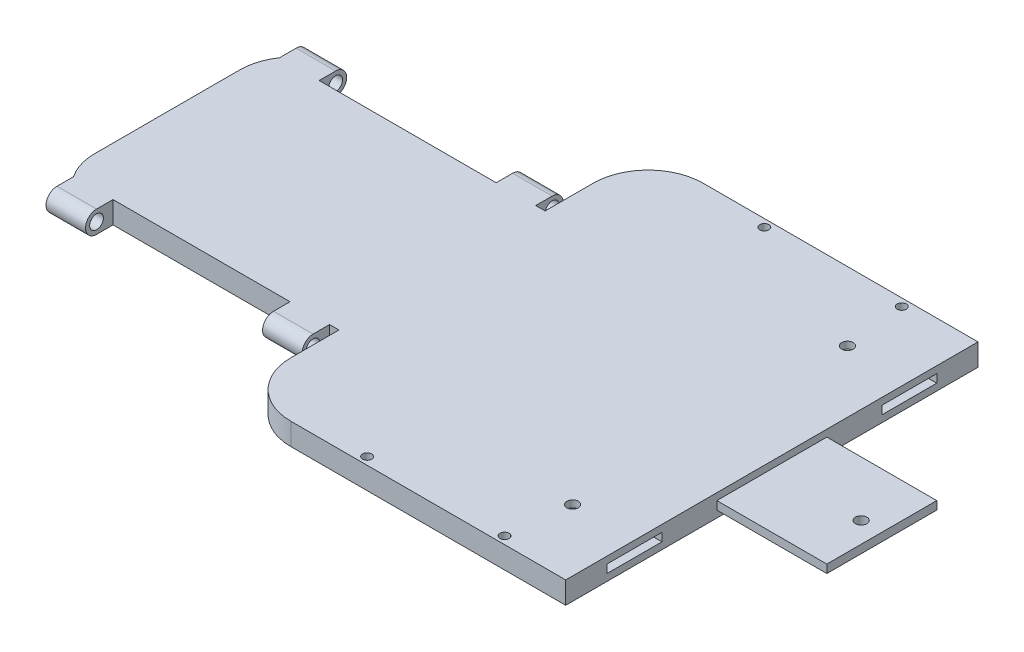
SolidWorks part; units mm, degrees
ref_plane "Front Plane" through (0, 0, 0) normal (0, 0, 1) x (1, 0, 0)
ref_plane "Top Plane" through (0, 0, 0) normal (0, 1, 0) x (1, 0, 0)
ref_plane "Right Plane" through (0, 0, 0) normal (1, 0, 0) x (0, 0, -1)
sketch "Sketch1" plane through (0, 0, 0) normal (0, 1, 0) x (1, 0, 0)
  line L0 (-120, -37.5) -> (-120, -75)
  line L1 (-120, 75) -> (0, 75)
  line L2 (-120, 75) -> (-120, 37.5)
  line L3 (-120, -75) -> (0, -75)
  line L5 (-120, 75) -> (0, 0) construction
  line L6 (0, 75) -> (0, -75)
  line L7 (-220, 37.5) -> (-120, 37.5)
  line L8 (-220, 37.5) -> (-220, -37.5)
  line L9 (-220, -37.5) -> (-120, -37.5)
  line L11 (-220, 37.5) -> (-120, -37.5) construction
  line L12 (-220, -37.5) -> (-120, 37.5) construction
  line L13 (-237.7651, 0) -> (0, 0) construction
  line L14 (0, 88.8927) -> (0, -90.7354) construction
  point P0 (0, 0)
  point P6 (-170, 0)
  dimension "D1" = 100
  dimension "D2" = 75
  dimension "D3" = 120
  dimension "D4" = 150
extrude "Boss-Extrude1" add sketch "Sketch1" along normal blind 8
ref_plane "Plane1" through (-170, 0, 0) normal (-1, 0, 0) x (0, 0, 1)
sketch "Sketch4" plane through (-170, 0, 0) normal (-1, 0, 0) x (0, 0, 1)
  line L0 (37.5, 8) -> (43.5, 8)
  line L1 (37.5, 0) -> (43.5, 0)
  line L2 (37.5, 8) -> (37.5, 0)
  line L3 (0, 17.6181) -> (0, -10.735) construction
  line L4 (-37.5, 0) -> (-43.5, 0)
  line L5 (-37.5, 8) -> (-37.5, 0)
  line L6 (-37.5, 8) -> (-43.5, 8)
  arc A0 (43.5, 0) -> (43.5, 8) centre (43.5, 4) ccw
  circle A1 centre (43.5, 4) radius 3.3
  circle A2 centre (-43.5, 4) radius 3.3
  arc A3 (-43.5, 0) -> (-43.5, 8) centre (-43.5, 4) cw
  dimension "D1" = 6
extrude "Boss-Extrude2" add sketch "Sketch4" along normal blind 46.584 and the other way blind 46.584
sketch "Sketch5" plane through (-170, 0, 0) normal (-1, 0, 0) x (0, 0, 1)
  line L9 (-43.5, 8) -> (-37.5, 8)
  line L10 (-37.5, 8) -> (-37.5, 0)
  line L11 (-37.5, 0) -> (-43.5, 0)
  line L12 (0, -5.7713) -> (0, 22.701) construction
  line L13 (37.5, 0) -> (43.5, 0)
  line L14 (37.5, 8) -> (37.5, 0)
  line L15 (43.5, 8) -> (37.5, 8)
  circle A20 centre (-43.5, 4) radius 3.3
  circle A21 centre (-43.5, 4) radius 3.3
  arc A22 (43.5, 8) -> (43.5, 0) centre (43.5, 4) cw
  arc A23 (-43.5, 8) -> (-43.5, 0) centre (-43.5, 4) ccw
  arc A24 (-43.5, 8) -> (-43.5, 0) centre (-43.5, 4) ccw
  circle A25 centre (43.5, 4) radius 3.3
  dimension "D1" = 0
  dimension "D2" = 0
extrude "Cut-Extrude1" cut sketch "Sketch5" against normal blind 32.2 and the other way blind 32.2
sketch "Sketch6" plane through (0, 0, 0) normal (1, 0, 0) x (0, 0, -1)
  line L0 (0, 8) -> (0, 0) construction
  line L1 (-75, 8) -> (75, 8) construction
  line L3 (-20, 5.5) -> (20, 5.5)
  line L4 (-20, 5.5) -> (-20, 2.5)
  line L5 (-20, 2.5) -> (20, 2.5)
  line L6 (20, 5.5) -> (20, 2.5)
  line L7 (-20, 5.5) -> (20, 2.5) construction
  line L8 (-20, 2.5) -> (20, 5.5) construction
  point P5 (0, 4)
  dimension "D1" = 40
  dimension "D2" = 2.5
  dimension "D3" = 3
extrude "Boss-Extrude3" add sketch "Sketch6" along normal blind 40
sketch "Sketch7" plane through (0, 5.5, 0) normal (0, 1, 0) x (1, 0, 0)
  line L0 (40, 20) -> (40, -20) construction
  circle A0 centre (32.75, 0) radius 2
  dimension "D1" = 4
  dimension "D2" = 7.25
extrude "Cut-Extrude2" cut sketch "Sketch7" against normal through all
sketch "Sketch8" plane through (0, 0, 0) normal (1, 0, 0) x (0, 0, -1)
  line L0 (0, 13.5629) -> (0, 0) construction
  line L2 (-75, 4) -> (0, 4) construction
  line L3 (-75, 8) -> (-75, 0) construction
  line L4 (-75, 8) -> (75, 8) construction
  line L5 (-60, 5.5) -> (-40, 5.5)
  line L6 (-60, 5.5) -> (-60, 2.5)
  line L7 (-60, 2.5) -> (-40, 2.5)
  line L8 (-40, 5.5) -> (-40, 2.5)
  line L9 (-60, 5.5) -> (-40, 2.5) construction
  line L10 (-60, 2.5) -> (-40, 5.5) construction
  line L11 (40, 5.5) -> (40, 2.5)
  line L12 (60, 5.5) -> (60, 2.5)
  line L13 (60, 5.5) -> (40, 5.5)
  line L14 (60, 2.5) -> (40, 2.5)
  point P3 (-50, 4)
  dimension "D1" = 2.5
  dimension "D2" = 20
  dimension "D3" = 15
extrude "Cut-Extrude3" cut sketch "Sketch8" against normal blind 30
sketch "Sketch9" plane through (0, 8, 0) normal (0, 1, 0) x (1, 0, 0)
  line L0 (-120, -75) -> (0, -75) construction
  line L1 (0, -75) -> (0, 75) construction
  line L2 (47.6902, 0) -> (-243.5934, 0) construction
  circle A0 centre (-22.5, -50) radius 2
  circle A1 centre (-22.5, 50) radius 2
  dimension "D1" = 25
  dimension "D2" = 22.5
extrude "Cut-Extrude4" cut sketch "Sketch9" against normal through all
fillet "Fillet1" radius 20 4 edges at (-220, 4, 37.5) (-220, 4, -37.5) (-120, 4, -75) (-120, 4, 75)
sketch "Sketch10" plane through (0, 8, 0) normal (0, 1, 0) x (1, 0, 0)
  line L0 (-75, 0) -> (16.9283, 0) construction
  line L4 (-100, 75) -> (-100, 70) construction
  line L7 (-100, 72.5) -> (0, 72.5) construction
  line L8 (0, -75) -> (0, 75) construction
  circle A0 centre (-25, 72.5) radius 1.5
  circle A1 centre (-75, 72.5) radius 1.5
  circle A2 centre (-25, -72.5) radius 1.5
  circle A5 centre (-75, -72.5) radius 1.5
  dimension "D3" = 25
  dimension "D4" = 25
extrude "Cut-Extrude5" cut sketch "Sketch10" against normal blind 10
scale "Scale1" scale about centroid uniform scaling yes scale factor 1.5
scale "Scale2" scale about centroid uniform scaling yes scale factor 0.8
sketch "Sketch12" plane through (0, 8.8, 0) normal (0, 1, 0) x (1, 0, 0)
  circle A0 centre (-71.6467, 87) radius 1.8
  circle A1 centre (-11.6467, 87) radius 1.8
  circle A2 centre (-11.6467, -87) radius 1.8
  circle A3 centre (-71.6467, -87) radius 1.8
extrude "Boss-Extrude4" add sketch "Sketch12" against normal through all
sketch "Sketch13" plane through (0, -0.8, 0) normal (0, -1, 0) x (1, 0, 0)
  line L0 (-101.6467, 90) -> (-101.6467, 83.4) construction
  line L1 (-101.6467, 83.4) -> (18.3533, 83.4) construction
  line L2 (18.3533, 90) -> (18.3533, -90) construction
  line L3 (18.3533, 83.4) -> (18.3533, 90) construction
  line L4 (-41.6467, 90) -> (-41.6467, 83.4) construction
  line L5 (-101.6467, 90) -> (18.3533, 90) construction
  line L6 (-101.6467, 86.7) -> (-41.6467, 86.7) construction
  line L7 (18.3533, 0) -> (-245.6467, 0) construction
  line L8 (18.3533, 24) -> (18.3533, -24) construction
  line L9 (-245.6467, -31.5851) -> (-245.6467, 31.5851) construction
  line L10 (-101.6467, -86.7) -> (-41.6467, -86.7) construction
  line L11 (-41.6467, -90) -> (-41.6467, -83.4) construction
  line L12 (18.3533, -83.4) -> (18.3533, -90) construction
  line L13 (-101.6467, -83.4) -> (18.3533, -83.4) construction
  line L14 (-101.6467, -90) -> (-101.6467, -83.4) construction
  circle A0 centre (-71.6467, 86.7) radius 2
  circle A1 centre (-11.6467, 86.7) radius 2
  circle A2 centre (-11.6467, -86.7) radius 2
  circle A3 centre (-71.6467, -86.7) radius 2
  circle A4 centre (-8.6467, 60) radius 2.5
  circle A5 centre (57.6533, 0) radius 2.5
  circle A6 centre (-8.6467, -60) radius 2.5
  dimension "D1" = 6.6
extrude "Cut-Extrude6" cut sketch "Sketch13" against normal through all
sketch "Sketch14" plane through (-241.5475, 0, 0) normal (-1, 0, 0) x (0, 0, 1)
  line L0 (0, -0.8) -> (0, 8.8) construction
  line L1 (-31.5851, -0.8) -> (31.5851, -0.8) construction
  line L2 (-31.5851, 8.8) -> (31.5851, 8.8) construction
  circle A0 centre (-52.2, 4) radius 4.2507
  circle A1 centre (-52.2, 4) radius 3
  circle A2 centre (52.2, 4) radius 3
  circle A3 centre (52.2, 4) radius 4.2507
extrude "Boss-Extrude5" add sketch "Sketch14" against normal up to surface (111.8015 mm away) up to face at (-129.746, 4, -56.16)
sketch "Sketch15" plane through (0, 8.8, 0) normal (0, 1, 0) x (1, 0, 0)
  line L0 (-147.0067, -52.2) -> (-147.0067, -45) construction
  line L1 (-224.2867, 57) -> (-147.0067, 57)
  line L2 (-224.2867, 57) -> (-224.2867, 45)
  line L3 (-224.2867, 45) -> (-147.0067, 45)
  line L4 (-147.0067, 57) -> (-147.0067, 45)
  line L5 (-224.2867, -57) -> (-147.0067, -57)
  line L6 (-224.2867, -57) -> (-224.2867, -45)
  line L7 (-224.2867, -45) -> (-147.0067, -45)
  line L8 (-147.0067, -57) -> (-147.0067, -45)
  line L9 (-224.2867, -45) -> (-147.0067, -45) construction
extrude "Cut-Extrude7" cut sketch "Sketch15" against normal through all
sketch "Sketch16" plane through (0, 5.8, 0) normal (0, 1, 0) x (1, 0, 0)
  circle A0 centre (57.6533, 0) radius 2.5
extrude "Boss-Extrude6" add sketch "Sketch16" against normal up to surface (3.6 mm away) up to face at (57.6533, 2.2, 2.5)
sketch "Sketch17" plane through (0, 5.8, 0) normal (0, 1, 0) x (1, 0, 0)
  line L0 (18.3533, 0) -> (57.3533, 0) construction
  line L1 (18.3533, 24) -> (18.3533, -24) construction
  circle A0 centre (57.3533, 0) radius 2.5
extrude "Cut-Extrude8" cut sketch "Sketch17" against normal through all
